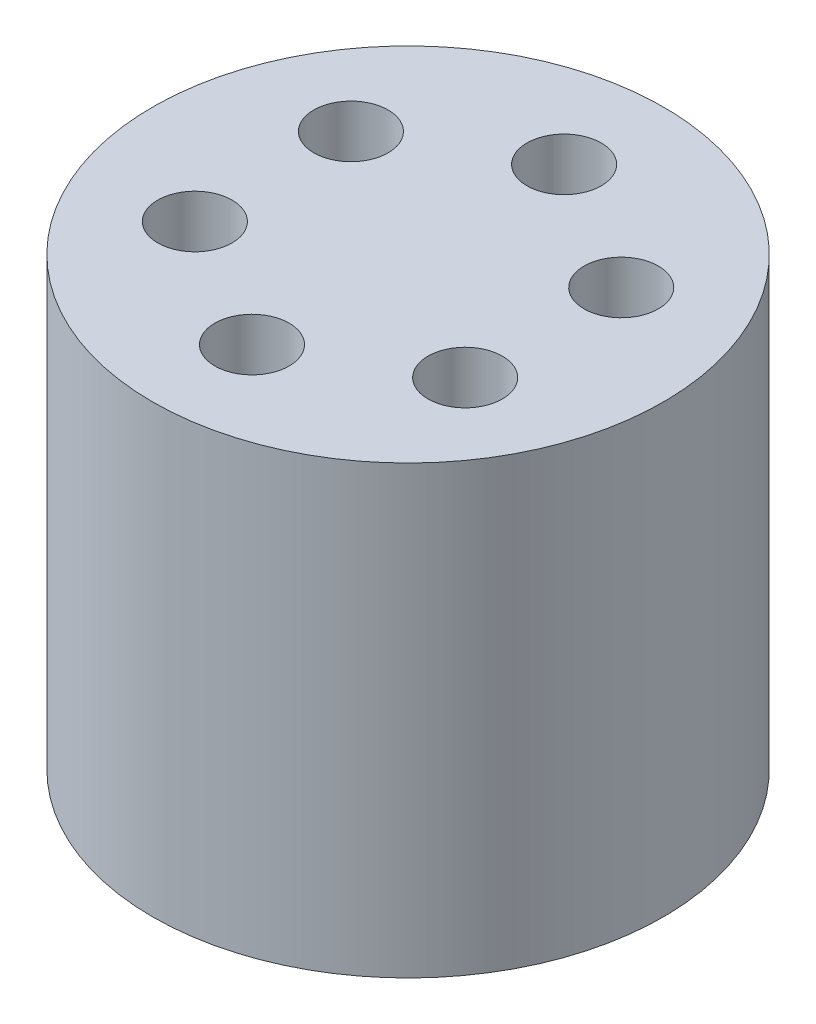
SolidWorks part; units mm, degrees
ref_plane "Front Plane" through (0, 0, 0) normal (0, 0, 1) x (1, 0, 0)
ref_plane "Top Plane" through (0, 0, 0) normal (0, 1, 0) x (1, 0, 0)
ref_plane "Right Plane" through (0, 0, 0) normal (1, 0, 0) x (0, 0, -1)
sketch "Sketch1" plane through (0, 0, 0) normal (0, 1, 0) x (1, 0, 0)
  circle A0 centre (0, 0) radius 18.9
extrude "Boss-Extrude1" add sketch "Sketch1" along normal blind 33
sketch "Sketch2" plane through (0, 33, 0) normal (0, 1, 0) x (1, 0, 0)
  line L1 (0, 11.547) -> (-10, 5.7735)
  line L2 (-10, 5.7735) -> (-10, -5.7735)
  line L3 (-10, -5.7735) -> (0, -11.547)
  line L4 (0, -11.547) -> (10, -5.7735)
  line L5 (10, -5.7735) -> (10, 5.7735)
  line L6 (10, 5.7735) -> (0, 11.547)
  circle A0 centre (0, 0) radius 10 construction
  circle A1 centre (0, 11.547) radius 2.75
  circle A2 centre (10, 5.7735) radius 2.75
  circle A3 centre (10, -5.7735) radius 2.75
  circle A4 centre (0, -11.547) radius 2.75
  circle A5 centre (-10, -5.7735) radius 2.75
  circle A6 centre (-10, 5.7735) radius 2.75
extrude "Cut-Extrude1" cut sketch "Sketch2" against normal blind 91.4 contours L1 A6 L2 | L2 A6 L1 | L6 A1 L1 | L1 A1 L6 | L5 A2 L6 | L6 A2 L5 | L4 A3 L5 | L5 A3 L4 | L3 A4 L4 | L4 A4 L3 | L2 A5 L3 | L3 A5 L2 region at (0, 33, -10.0309) region at (0, 33, -12.3051) region at (-8.687, 33, -5.0154) region at (-10.6565, 33, -6.1525) region at (10.6565, 33, -6.1525) region at (8.687, 33, -5.0154) region at (-8.687, 33, 5.0154) region at (-10.6565, 33, 6.1525) region at (10.6565, 33, 6.1525) region at (8.687, 33, 5.0154) region at (0, 33, 10.0309) region at (0, 33, 12.3051)
